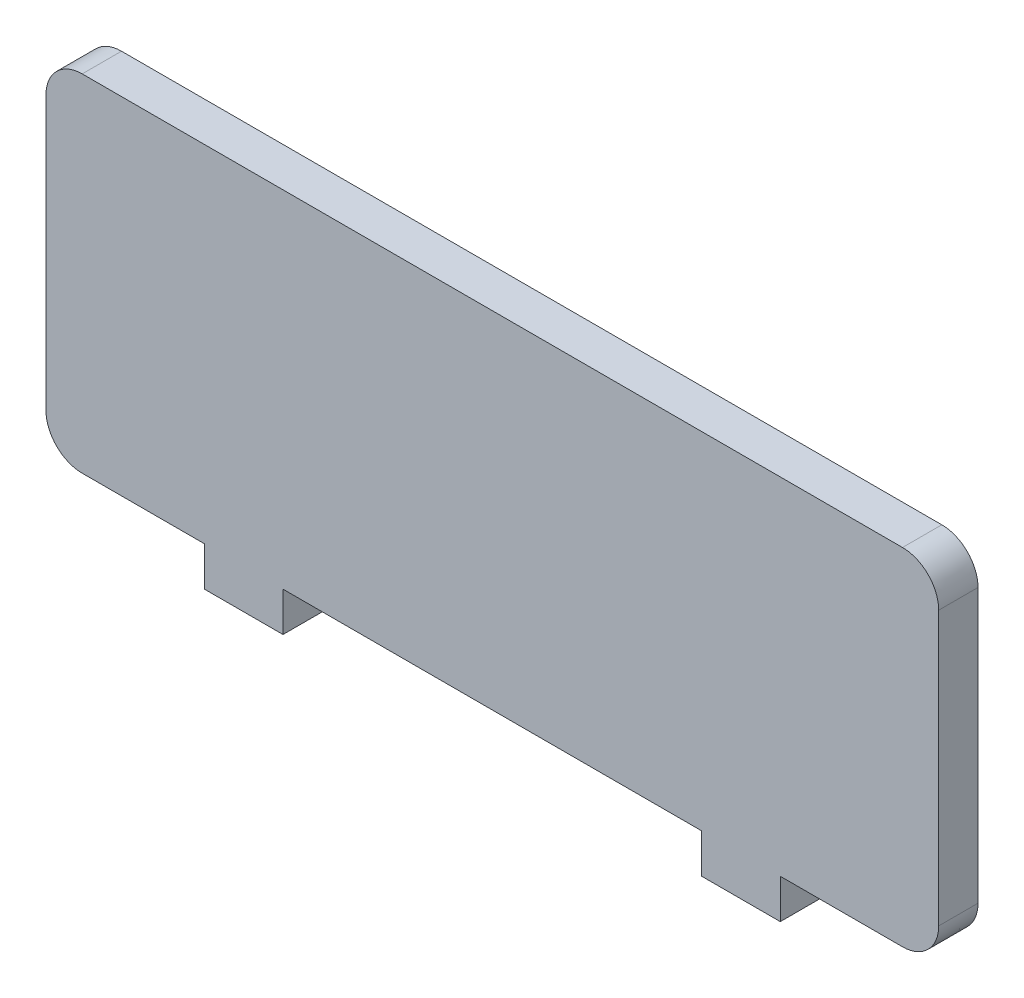
SolidWorks part; units mm, degrees
ref_plane "Front Plane" through (0, 0, 0) normal (0, 0, 1) x (1, 0, 0)
ref_plane "Top Plane" through (0, 0, 0) normal (0, 1, 0) x (1, 0, 0)
ref_plane "Right Plane" through (0, 0, 0) normal (1, 0, 0) x (0, 0, -1)
sketch "Model" plane through (0, 0, 0) normal (0, 0, 1) x (1, 0, 0)
  line L0 (286.9237, -389.0943) -> (238.9237, -389.0943)
  line L1 (236.8055, -391.2123) -> (236.8055, -407.2124)
  line L2 (238.9237, -409.3304) -> (286.9237, -409.3304)
  line L3 (289.0418, -407.2124) -> (289.0418, -391.2123)
  spline S0 degree 3 poles (238.9237, -389.0943) (237.7558, -389.0943) (236.8055, -390.0444) (236.8055, -391.2123) knots 1 1 1 1 2 2 2 2
  spline S1 degree 3 poles (236.8055, -407.2124) (236.8055, -408.3802) (237.7558, -409.3304) (238.9237, -409.3304) knots 3 3 3 3 4 4 4 4
  spline S2 degree 3 poles (286.9237, -409.3304) (288.0916, -409.3304) (289.0418, -408.3802) (289.0418, -407.2124) knots 5 5 5 5 6 6 6 6
  spline S3 degree 3 poles (289.0418, -391.2123) (289.0418, -390.0444) (288.0916, -389.0943) (286.9237, -389.0943) knots 7 7 7 7 8 8 8 8
base flange "Base-Flange1" sketch "Model" thickness 2.3 reverse thickness direction no parameters "D1"=0.7366
sketch "Sketch6" plane through (0, 0, 0) normal (0, 0, 1) x (1, 0, 0)
  line L0 (238.9237, -409.3304) -> (286.9237, -409.3304) construction
  line L1 (246.0737, -409.3304) -> (250.6737, -409.3304)
  line L2 (246.0737, -409.3304) -> (246.0737, -411.6304)
  line L3 (246.0737, -411.6304) -> (250.6737, -411.6304)
  line L4 (250.6737, -409.3304) -> (250.6737, -411.6304)
  line L5 (262.9237, -409.3304) -> (262.9237, -403.2082) construction
  line L6 (275.1737, -409.3304) -> (275.1737, -411.6304)
  line L7 (279.7737, -411.6304) -> (275.1737, -411.6304)
  line L8 (279.7737, -409.3304) -> (279.7737, -411.6304)
  line L9 (279.7737, -409.3304) -> (275.1737, -409.3304)
  dimension "D1" = 4.6
  dimension "D2" = 2.3
  dimension "D3" = 12.25
base flange "Tab1" sketch "Sketch6" thickness 2.3 reverse thickness direction no parameters "D1"=0.7366
sketch "Bend-Lines1" [suppressed] plane through (0, 0, 0) normal (0, 1, 0) x (1, 0, 0)
sketch "Bounding-Box1" [suppressed] plane through (0, 0, 0) normal (0, 1, 0) x (1, 0, 0)
sheet metal parameters "Sheet-Metal1" thickness 2.3 parameters "D1"=0.7366
flat pattern "Flat-Pattern1" [suppressed]
sketch "Bend-Lines2" plane through (0, 0, 0) normal (0, 1, 0) x (1, 0, 0)
sketch3d "Bounding-Box2" [suppressed]
  line L0 (0.6211, -19.6151, 0) -> (-51.6151, -19.6151, 0) construction
  line L1 (0.6211, 0.6211, 0) -> (-51.6151, 0.6211, 0) construction
  line L2 (0.6211, -19.6151, 0) -> (0.6211, 0.6211, 0) construction
  line L3 (-51.6151, -19.6151, 0) -> (-51.6151, 0.6211, 0) construction
sheet metal parameters "Sheet-Metal2" thickness 2.3 parameters "D1"=0.7366
flat pattern "Flat-Pattern2"
sketch "Bend-Lines3" plane through (0, 0, 0) normal (0, 1, 0) x (1, 0, 0)
sketch3d "Bounding-Box3" [suppressed]
  line L0 (-0.6211, -21.9151, 0) -> (51.6151, -21.9151, 0) construction
  line L1 (-0.6211, 0.6211, 0) -> (51.6151, 0.6211, 0) construction
  line L2 (-0.6211, -21.9151, 0) -> (-0.6211, 0.6211, 0) construction
  line L3 (51.6151, -21.9151, 0) -> (51.6151, 0.6211, 0) construction
